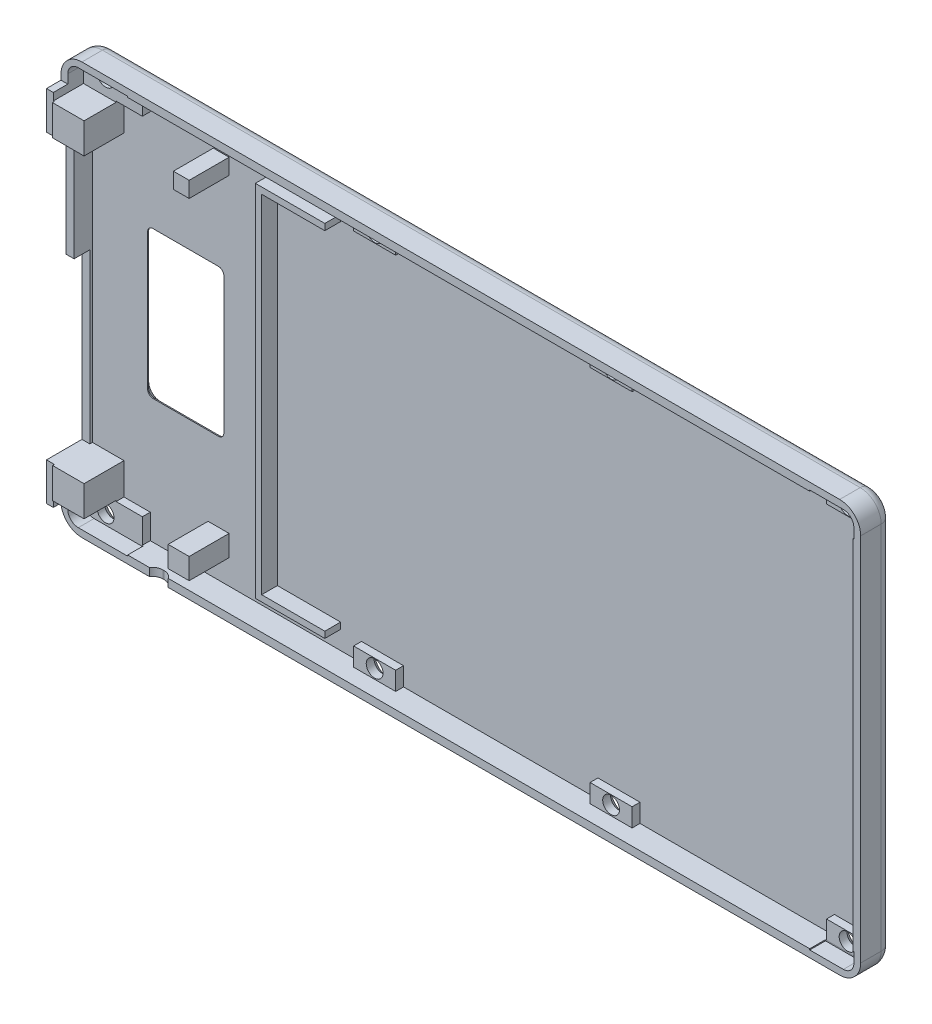
SolidWorks part; units mm, degrees
ref_plane "Plan de face" through (0, 0, 0) normal (0, 0, 1) x (1, 0, 0)
ref_plane "Plan de dessus" through (0, 0, 0) normal (0, 1, 0) x (1, 0, 0)
ref_plane "Plan de droite" through (0, 0, 0) normal (1, 0, 0) x (0, 0, -1)
sketch "Esquisse1" plane through (0, 0, 0) normal (0, 0, 1) x (1, 0, 0)
  line L0 (149.2, 71.9) -> (34, 71.9)
  line L1 (0, 0) -> (149.2, 0)
  line L2 (0, 0) -> (0, 75.4)
  line L3 (0, 75.4) -> (149.2, 75.4)
  line L4 (149.2, 0) -> (149.2, 75.4)
  line L5 (34, 71.9) -> (34, 3.5)
  line L6 (34, 3.5) -> (149.2, 3.5)
  line L7 (149.2, 70.7) -> (35.2, 70.7)
  line L8 (35.2, 70.7) -> (35.2, 4.7)
  line L9 (35.2, 4.7) -> (149.2, 4.7)
  line L10 (-19.055, 37.7) -> (204.5006, 37.7) construction
  line L11 (-1.5, 76.9) -> (150.7, 76.9)
  line L12 (-1.5, 76.9) -> (-1.5, -1.5)
  line L13 (-1.5, -1.5) -> (150.7, -1.5)
  line L14 (150.7, 76.9) -> (150.7, -1.5)
  line L15 (0, 72.1) -> (0, 70.7)
  line L16 (26, 70.7) -> (0, 70.7)
  line L17 (26, 70.7) -> (26, 4.7)
  line L18 (26, 4.7) -> (0, 4.7)
  line L19 (0, 70.7) -> (0, 4.7)
  line L20 (1.4, 69.3) -> (24.6, 69.3)
  line L21 (1.4, 69.3) -> (1.4, 6.1)
  line L22 (1.4, 6.1) -> (24.6, 6.1)
  line L23 (24.6, 69.3) -> (24.6, 6.1)
  line L24 (0, 72.1) -> (27.4, 72.1)
  line L25 (0, 3.3) -> (0, 4.7)
  line L26 (0, 3.3) -> (27.4, 3.3)
  line L27 (27.4, 72.1) -> (27.4, 3.3)
  line L28 (141.2, 75.4) -> (141.2, 71.9)
  line L29 (0, 4.7) -> (6, 4.7)
  line L30 (0, 4.7) -> (0, 10.7)
  line L31 (0, 10.7) -> (6, 10.7)
  line L32 (6, 4.7) -> (6, 10.7)
  line L33 (26, 4.7) -> (22, 4.7)
  line L34 (26, 4.7) -> (26, 8.7)
  line L35 (26, 8.7) -> (22, 8.7)
  line L36 (22, 4.7) -> (22, 8.7)
  line L37 (0, 70.7) -> (6, 70.7)
  line L38 (0, 70.7) -> (0, 64.7)
  line L39 (0, 64.7) -> (6, 64.7)
  line L40 (6, 70.7) -> (6, 64.7)
  line L41 (26, 70.7) -> (23, 70.7)
  line L42 (26, 70.7) -> (26, 67.7)
  line L43 (26, 67.7) -> (23, 67.7)
  line L44 (23, 70.7) -> (23, 67.7)
  line L45 (104.2, 75.4) -> (104.2, 71.9)
  line L46 (96.2, 75.4) -> (96.2, 71.9)
  line L47 (59.2, 75.4) -> (59.2, 71.9)
  line L48 (51.2, 75.4) -> (51.2, 71.9)
  line L49 (141.2, 0) -> (141.2, 3.5)
  line L50 (104.2, 0) -> (104.2, 3.5)
  line L51 (96.2, 0) -> (96.2, 3.5)
  line L52 (59.2, 0) -> (59.2, 3.5)
  line L53 (51.2, 0) -> (51.2, 3.5)
  circle A0 centre (145.2, 73.6) radius 1.25
  circle A3 centre (100.2, 73.6) radius 1.25
  circle A5 centre (55.2, 73.6) radius 1.25
  circle A6 centre (145.2, 1.8) radius 1.25
  circle A8 centre (100.2, 1.8) radius 1.25
  circle A11 centre (55.2, 1.8) radius 1.25
  dimension "D12" = 2.5
  dimension "D13" = 4
  dimension "D1" = 1.5
  dimension "D3" = 1.2
  dimension "D4" = 1.2
  dimension "D5" = 1.2
  dimension "D6" = 66
  dimension "D7" = 3.5
  dimension "D8" = 114
  dimension "D9" = 1.5
  dimension "D10" = 1.5
  dimension "D11" = 1.5
  dimension "D15" = 33
  dimension "D16" = 33
  dimension "D17" = 1.8
  dimension "D18" = 66
  dimension "D19" = 26
  dimension "D20" = 33
  dimension "D21" = 33
  dimension "D22" = 8
  dimension "D23" = 1.4
  dimension "D24" = 1.4
  dimension "D25" = 1.4
  dimension "D26" = 1.4
  dimension "D27" = 1.4
  dimension "D28" = 0
  dimension "D29" = 1.4
  dimension "D30" = 1.4
  dimension "D31" = 4
  dimension "D32" = 0
  dimension "D33" = 0
  dimension "D34" = 6
  dimension "D35" = 6
  dimension "D36" = 4
  dimension "D37" = 4
  dimension "D38" = 6
  dimension "D39" = 6
  dimension "D40" = 3
  dimension "D41" = 3
  dimension "D42" = 4
  dimension "D43" = 4
  dimension "D44" = 4
  dimension "D45" = 4
  dimension "D46" = 3.5
  dimension "D47" = 45
  dimension "D14" = 3
extrude "Boss.-Extru.1" add sketch "Esquisse1" along normal blind 5.9 contours L12 L10 L2 L3 L4 L14 L11 | L10 L12 L13 L14 L4 L1 L2 region at (149.3572, 73.65, 0) region at (149.95, 36.1283, 0)
extrude "Boss.-Extru.2" add sketch "Esquisse1<4>" along normal blind 1.4 contours L3 L4 L1 L2
sketch "Esquisse1<4>" plane through (0, 0, 0) normal (0, 0, 1) x (1, 0, 0) same geometry as "Esquisse1"
extrude "Boss.-Extru.5" add sketch "Esquisse1<5>" along normal blind 1.5 from surface separate body contours A5 | A3 | A0 | A11 | A8 | A6 region at (145.2, 71.9873, 0) region at (100.2, 71.9873, 0) region at (149.1127, 1.75, 0) region at (55.2, 71.9873, 0) region at (104.1127, 1.75, 0) region at (59.1127, 1.75, 0) starting at face at (74.6, 37.7, 1.4)
sketch "Esquisse1<5>" plane through (0, 0, 0) normal (0, 0, 1) x (1, 0, 0) same geometry as "Esquisse1"
extrude "Boss.-Extru.7" add sketch "Esquisse1<6>" along normal blind 3 from surface contours L5 L10 L8 L7 L4 L0 | L10 L5 L6 L4 L9 L8 region at (147.9983, 71.3, 0) region at (147.9983, 4.1, 0) starting at face at (74.6, 37.7, 1.4)
sketch "Esquisse1<6>" plane through (0, 0, 0) normal (0, 0, 1) x (1, 0, 0) same geometry as "Esquisse1"
fillet "Congé1" radius 4 4 edges at (-1.5, 76.9, 2.95) (-1.5, -1.5, 2.95) (150.7, -1.5, 2.95) (150.7, 76.9, 2.95)
fillet "Congé2" radius 2 4 edges at (0, 0, 3.65) (149.2, 0, 3.65) (149.2, 75.4, 3.65) (0, 75.4, 3.65)
sketch "Esquisse4" plane through (0, 0, 0) normal (0, 0, -1) x (-1, 0, 0)
  circle A0 centre (-55.2, 1.8) radius 1.6
  circle A1 centre (-100.2, 1.8) radius 1.6
  circle A2 centre (-145.2, 1.8) radius 1.6
  circle A3 centre (-145.2, 73.6) radius 1.6
  circle A4 centre (-100.2, 73.6) radius 1.6
  circle A5 centre (-55.2, 73.6) radius 1.6
  dimension "D1" = 3.2
  dimension "D2" = 3.2
  dimension "D3" = 3.2
  dimension "D4" = 3.2
  dimension "D5" = 3.2
  dimension "D6" = 3.2
extrude "Enlèv. mat.-Extru.2" cut sketch "Esquisse4" against normal blind 60.5 and the other way blind 4.3
extrude "Boss.-Extru.9" add sketch "Esquisse1<9>" along normal blind 7.6 from surface contours L38 L39 L40 L37 | L42 L43 L44 L41 | L30 L31 L32 L29 | L34 L35 L36 L33 starting at face at (98.6, 1.8, 1.4)
sketch "Esquisse1<9>" plane through (0, 0, 0) normal (0, 0, 1) x (1, 0, 0) same geometry as "Esquisse1"
sketch "Esquisse5" plane through (0, 0, 1.4) normal (0, 0, 1) x (1, 0, 0)
  line L1 (11, 70.7) -> (0, 70.7)
  line L2 (11, 70.7) -> (11, 75.4)
  line L3 (11, 75.4) -> (0, 75.4)
  line L4 (0, 70.7) -> (0, 75.4)
  line L5 (11, 4.7) -> (0, 4.7)
  line L6 (11, 4.7) -> (11, 0)
  line L7 (11, 0) -> (0, 0)
  line L8 (0, 4.7) -> (0, 0)
  line L9 (2, 75.4) -> (147.2, 75.4) construction
  line L10 (0, 4.7) -> (6, 4.7) construction
  line L11 (0, 70.7) -> (6, 70.7) construction
  dimension "D1" = 0
  dimension "D2" = 0
  dimension "D3" = 0
  dimension "D4" = 11
  dimension "D5" = 11
extrude "Boss.-Extru.10" add sketch "Esquisse5" along normal blind 1.5
sketch "Esquisse6" plane through (0, 0, 0) normal (0, 0, -1) x (-1, 0, 0)
  line L7 (-11, 70.7) -> (-11, 75.4) construction
  line L8 (-11, 0) -> (-11, 4.7) construction
  circle A0 centre (-4, 1.8) radius 1.6
  circle A1 centre (-4, 73.6) radius 1.6
  circle A2 centre (-55.2, 73.6) radius 1.6 construction
  circle A3 centre (-55.2, 1.8) radius 1.6 construction
  dimension "D1" = 3.2
  dimension "D2" = 3.2
  dimension "D3" = 7
  dimension "D4" = 0
  dimension "D5" = 7
  dimension "D6" = 0
extrude "Enlèv. mat.-Extru.3" cut sketch "Esquisse6" against normal blind 40
chamfer "Chanfrein3" distance 1.48 angle 45 8 edges at (2.4, 1.8, 0) (2.4, 73.6, 0) (56.8, 1.8, 0) (101.8, 1.8, 0) (146.8, 1.8, 0) (146.8, 73.6, 0) (101.8, 73.6, 0) (56.8, 73.6, 0)
sketch "Esquisse9" plane through (0, 0, 0) normal (0, 0, -1) x (-1, 0, 0)
  line L0 (1.5, 72.9) -> (1.5, 2.5) construction
  line L1 (-11.5, 23.7) -> (-24, 23.7)
  line L2 (-10.5, 24.7) -> (-10.5, 50.7)
  line L3 (-11.5, 51.7) -> (-24, 51.7)
  line L4 (-25, 24.7) -> (-25, 50.7)
  line L5 (-2.5, -1.5) -> (-146.7, -1.5) construction
  line L6 (-2.5, 76.9) -> (-146.7, 76.9) construction
  arc A0 (-10.5, 50.7) -> (-11.5, 51.7) centre (-11.5, 50.7) ccw
  arc A1 (-24, 51.7) -> (-25, 50.7) centre (-24, 50.7) ccw
  arc A2 (-24, 23.7) -> (-25, 24.7) centre (-24, 24.7) cw
  arc A3 (-11.5, 23.7) -> (-10.5, 24.7) centre (-11.5, 24.7) ccw
  point P12 (-10.5, 51.7)
  point P15 (-25, 51.7)
  point P20 (-10.5, 23.7)
  dimension "D6" = 1
  dimension "D1" = 28
  dimension "D2" = 14.5
  dimension "D3" = 12
  dimension "D4" = 25.2
  dimension "D5" = 25.2
extrude "Enlèv. mat.-Extru.6" cut sketch "Esquisse9" against normal blind 1.4
sketch "Esquisse10" plane through (0, -1.5, 0) normal (0, -1, 0) x (1, 0, 0)
  line L1 (17.25, 9.25) -> (17, 9.25)
  line L2 (19.25, 7.25) -> (19.25, 7)
  line L3 (17.25, 5) -> (17, 5)
  line L4 (15, 7.25) -> (15, 7)
  line L9 (0, 9) -> (6, 9) construction
  line L10 (2.5, 5.9) -> (2.5, 0) construction
  arc A0 (17.25, 9.25) -> (19.25, 7.25) centre (17.25, 7.25) cw
  arc A1 (19.25, 7) -> (17.25, 5) centre (17.25, 7) cw
  arc A2 (17, 5) -> (15, 7) centre (17, 7) cw
  arc A3 (17, 9.25) -> (15, 7.25) centre (17, 7.25) ccw
  point P12 (19.25, 5)
  point P15 (15, 5)
  dimension "D5" = 2
  dimension "D1" = 4.25
  dimension "D2" = 4
  dimension "D3" = 12.5
  dimension "D4" = 4.25
extrude "Enlèv. mat.-Extru.7" cut sketch "Esquisse10" against normal blind 3
chamfer "Chanfrein4" distance 1.2 angle 45 8 edges at (10.5, 37.7, 0) (10.7929, 51.4071, 0) (10.7929, 23.9929, 0) (17.75, 51.7, 0) (17.75, 23.7, 0) (24.7071, 51.4071, 0) (24.7071, 23.9929, 0) (25, 37.7, 0)
fillet "Congé3" radius 2 8 edges at (-0.3284, -0.3284, 0) (-1.5, 37.7, 0) (-0.3284, 75.7284, 0) (74.6, 76.9, 0) (149.5284, 75.7284, 0) (150.7, 37.7, 0) (149.5284, -0.3284, 0) (74.6, -1.5, 0)
sketch "Esquisse11" plane through (0, 0, 5.9) normal (0, 0, 1) x (1, 0, 0)
  line L0 (-1.5, 72.9) -> (-1.5, 2.5) construction
  line L1 (0, 64.7) -> (-1.5, 64.7)
  line L2 (0, 64.7) -> (0, 71.9)
  line L3 (0, 71.9) -> (-1.5, 71.9)
  line L4 (-1.5, 64.7) -> (-1.5, 71.9)
  line L6 (0, 10.7) -> (-1.5, 10.7)
  line L7 (0, 10.7) -> (0, 3.5)
  line L8 (0, 3.5) -> (-1.5, 3.5)
  line L9 (-1.5, 10.7) -> (-1.5, 3.5)
  dimension "D1" = 7.2
  dimension "D2" = 7.2
extrude "Boss.-Extru.11" add sketch "Esquisse11" along normal blind 2.75
sketch "Esquisse12" plane through (0, 0, 5.9) normal (0, 0, 1) x (1, 0, 0)
  line L1 (0, 10.7) -> (-1.5, 10.7)
  line L2 (0, 10.7) -> (0, 42.7)
  line L3 (0, 42.7) -> (-1.5, 42.7)
  line L4 (-1.5, 10.7) -> (-1.5, 42.7)
  dimension "D1" = 32
extrude "Enlèv. mat.-Extru.8" cut sketch "Esquisse12" against normal blind 4
sketch "Esquisse13" plane through (0, 0, 5.9) normal (0, 0, 1) x (1, 0, 0)
  line L1 (-1.5, 42.7) -> (0, 42.7)
  line L2 (-1.5, 42.7) -> (-1.5, 64.7)
  line L3 (-1.5, 64.7) -> (0, 64.7)
  line L4 (0, 42.7) -> (0, 64.7)
extrude "Enlèv. mat.-Extru.9" cut sketch "Esquisse13" against normal blind 1
sketch "Esquisse16" plane through (0, 0, 4.4) normal (0, 0, 1) x (1, 0, 0)
  line L0 (149.2, 71.9) -> (34, 71.9) construction
  line L1 (47.2208, 71.9) -> (149.2, 71.9)
  line L2 (47.2208, 71.9) -> (47.2208, 70.7)
  line L3 (47.2208, 70.7) -> (149.2, 70.7)
  line L4 (149.2, 71.9) -> (149.2, 70.7)
  line L5 (35.2, 4.7) -> (149.2, 4.7) construction
  line L6 (47.2208, 4.7) -> (149.2, 4.7)
  line L7 (47.2208, 4.7) -> (47.2208, 3.5)
  line L8 (47.2208, 3.5) -> (149.2, 3.5)
  line L9 (149.2, 4.7) -> (149.2, 3.5)
extrude "Enlèv. mat.-Extru.11" cut sketch "Esquisse16" against normal blind 3
sketch "Esquisse14" plane through (0, 0, 8.65) normal (0, 0, 1) x (1, 0, 0)
  line L0 (-0.2, 4.9) -> (11.2, 4.9)
  line L1 (11.2, 4.9) -> (11.2, -0.2)
  line L2 (11.2, -0.2) -> (1.8, -0.2)
  line L3 (-0.2, 1.8) -> (-0.2, 4.9)
  line L4 (0, 2) -> (0, 3.5) construction
  line L5 (0, 4.7) -> (6, 4.7) construction
  line L6 (11, 0) -> (11, 4.7) construction
  line L7 (2, 0) -> (15.3297, 0) construction
  line L8 (-0.2, 70.5) -> (11.2, 70.5)
  line L9 (11.2, 70.5) -> (11.2, 75.6)
  line L10 (11.2, 75.6) -> (1.8, 75.6)
  line L11 (-0.2, 73.6) -> (-0.2, 70.5)
  line L12 (0, 73.4) -> (0, 70.7) construction
  line L13 (0, 70.7) -> (6, 70.7) construction
  line L14 (11, 70.7) -> (11, 75.4) construction
  line L15 (2, 75.4) -> (147.2, 75.4) construction
  line L16 (141, 75.6) -> (141, 71.7)
  line L17 (141, 71.7) -> (149.4, 71.7)
  line L18 (149.4, 71.7) -> (149.4, 73.6)
  line L19 (147.4, 75.6) -> (141, 75.6)
  line L20 (141.2, 75.4) -> (141.2, 71.9) construction
  line L21 (149.2, 71.9) -> (141.2, 71.9) construction
  line L22 (141.2, 75.4) -> (149.2, 75.4) construction
  line L23 (149.2, 2) -> (149.2, 73.4) construction
  line L24 (141, -0.2) -> (147.4, -0.2)
  line L25 (149.4, 1.8) -> (149.4, 3.7)
  line L26 (149.4, 3.7) -> (141, 3.7)
  line L27 (141, 3.7) -> (141, -0.2)
  line L28 (141.2, 0) -> (141.2, 3.5) construction
  line L29 (141.2, 0) -> (149.2, 0) construction
  line L30 (141.2, 3.5) -> (149.2, 3.5) construction
  line L31 (149.2, 0) -> (149.2, 3.5) construction
  arc A0 (1.8, -0.2) -> (-0.2, 1.8) centre (1.8, 1.8) cw
  arc A1 (1.8, 75.6) -> (-0.2, 73.6) centre (1.8, 73.6) ccw
  arc A2 (149.4, 73.6) -> (147.4, 75.6) centre (147.4, 73.6) ccw
  arc A3 (147.4, -0.2) -> (149.4, 1.8) centre (147.4, 1.8) ccw
  dimension "D1" = 2
  dimension "D10" = 2
  dimension "D15" = 2
  dimension "D20" = 2
  dimension "D2" = 0.2
  dimension "D3" = 0.2
  dimension "D4" = 0.2
  dimension "D5" = 0.2
  dimension "D6" = 0.2
  dimension "D7" = 0.2
  dimension "D8" = 0.2
  dimension "D9" = 0.2
  dimension "D11" = 0.2
  dimension "D12" = 0.2
  dimension "D13" = 0.2
  dimension "D14" = 0.2
  dimension "D16" = 0.2
  dimension "D17" = 0.2
  dimension "D18" = 0.2
  dimension "D19" = 0.2
extrude "Enlèv. mat.-Extru.10" cut sketch "Esquisse14" against normal blind 5.75 and the other way blind 5.7
